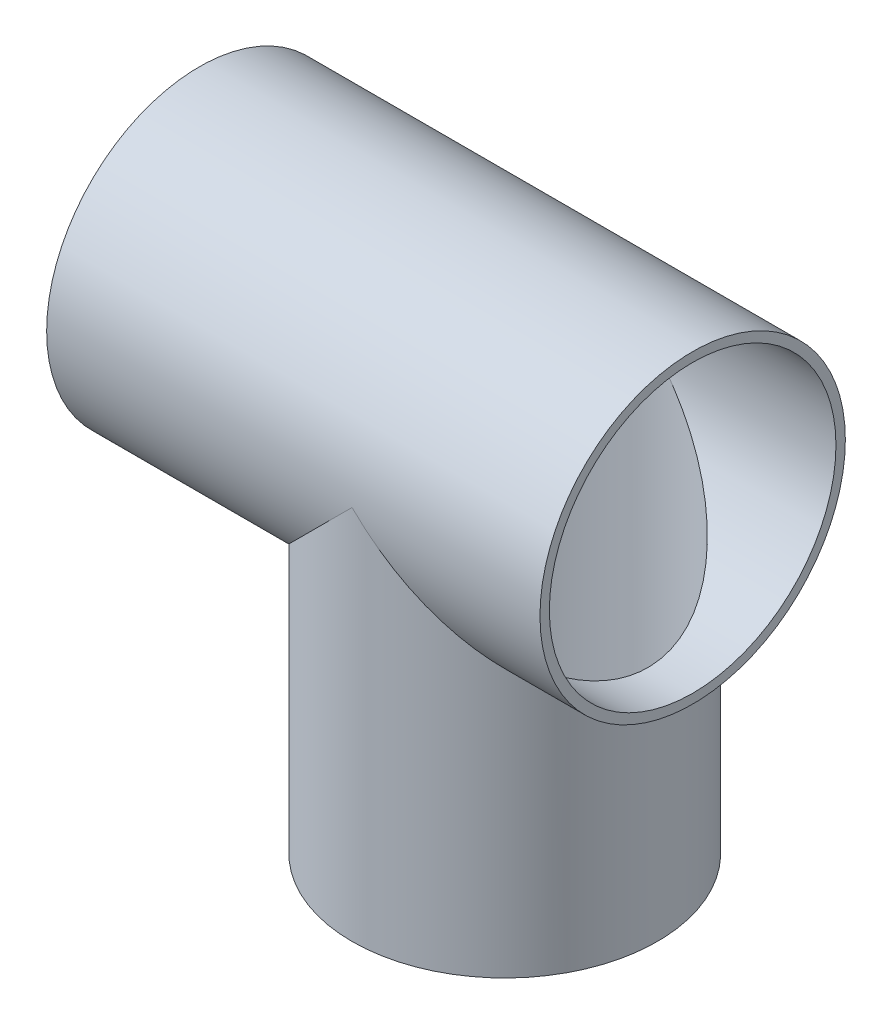
SolidWorks part; units mm, degrees
ref_plane "Front Plane" through (0, 0, 0) normal (0, 0, 1) x (1, 0, 0)
ref_plane "Top Plane" through (0, 0, 0) normal (0, 1, 0) x (1, 0, 0)
ref_plane "Right Plane" through (0, 0, 0) normal (1, 0, 0) x (0, 0, -1)
sketch "Sketch1" plane through (0, 0, 0) normal (1, 0, 0) x (0, 0, -1)
  circle A0 centre (0, 0) radius 32.5
  circle A1 centre (0, 0) radius 30.5
  dimension "D1" = 2
  dimension "D2" = 61
extrude "Boss-Extrude1" add sketch "Sketch1" along normal blind 40 and the other way blind 40
sketch "Sketch2" plane through (0, 0, 0) normal (0, 1, 0) x (1, 0, 0)
  circle A0 centre (0, 0) radius 30.5
  circle A1 centre (0, 0) radius 32.5
  dimension "D1" = 2
  dimension "D2" = 61
extrude "Boss-Extrude2" add sketch "Sketch2" against normal blind 80
sketch "Sketch3" plane through (40, 0, 0) normal (1, 0, 0) x (0, 0, -1)
  circle A0 centre (0, 0) radius 30.5
extrude "Cut-Extrude1" cut sketch "Sketch3" against normal blind 80
sketch "Sketch4" plane through (0, -80, 0) normal (0, -1, 0) x (1, 0, 0)
  circle A0 centre (0, 0) radius 30.5
extrude "Cut-Extrude2" cut sketch "Sketch4" against normal blind 79
sketch "Sketch5" plane through (-40, 0, 0) normal (-1, 0, 0) x (0, 0, 1)
  circle A0 centre (0, 0) radius 30.5
  circle A1 centre (0, 0) radius 32.5
  circle A2 centre (0, 0) radius 32.5
  dimension "D1" = 0
extrude "Boss-Extrude3" add sketch "Sketch5" along normal blind 25
